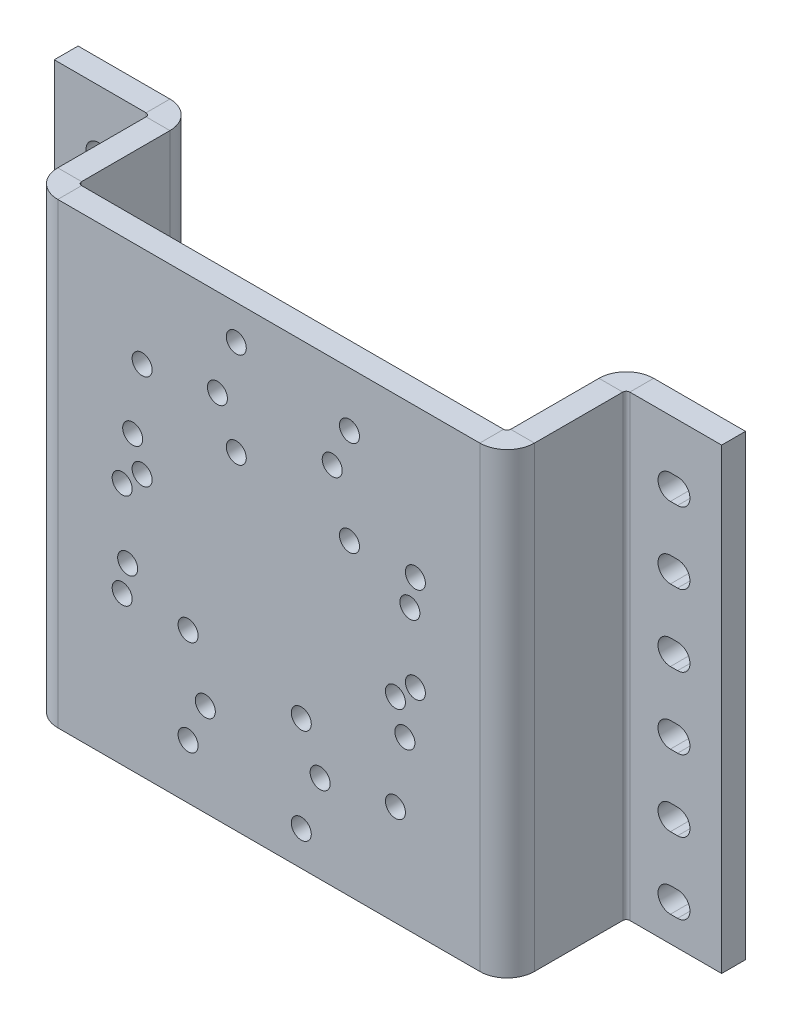
SolidWorks part; units mm, degrees
note: '?' marks a value the reader was unsure of. The reader was unsure of these and kept them because the rebuilt part matched: flange length of "Aresta-Flange1", "Aresta-Flange2", "Aresta-Flange3", "Aresta-Flange4".
material "AISI 1020"
ref_plane "Plano frontal" through (0, 0, 0) normal (0, 0, 1) x (1, 0, 0)
ref_plane "Plano superior" through (0, 0, 0) normal (0, 1, 0) x (1, 0, 0)
ref_plane "Plano direito" through (0, 0, 0) normal (1, 0, 0) x (0, 0, -1)
sketch "Esboço1" plane through (0, 0, 0) normal (0, 0, 1) x (1, 0, 0)
  line L1 (-50, 48) -> (50, 48)
  line L2 (-50, 48) -> (-50, -48)
  line L3 (-50, -48) -> (50, -48)
  line L4 (50, 48) -> (50, -48)
  line L5 (-50, 48) -> (50, -48) construction
  line L6 (-50, -48) -> (50, 48) construction
  point P0 (0, 0)
  dimension "D1" = 100
  dimension "D2" = 96
base flange "Flange-base1" sketch "Esboço1" thickness 5 reverse thickness direction no parameters "D1"=0.7366
edge flange "Aresta-Flange1" sketch "Esboço8" flange angle 90 flange length 30 flange position material inside bend radius 0.7366 thickness 5 relief rectangular parameters "D6"=10
sketch "Esboço8" plane through (50, 0, -5) normal (-1, 0, 0) x (0, 1, 0)
  line L2 (-48, 0) -> (-48, 25)
  line L3 (-48, 25) -> (48, 25)
  line L4 (48, 25) -> (48, 0)
  line L5 (48, 0) -> (-48, 0) construction
  line L6 (48, 0) -> (-48, 0)
bend "DobradeAresta1" bend radius 0.7366 bend angle 90 parameters "D5"=1
edge flange "Aresta-Flange2" sketch "Esboço11" flange angle 90 flange length 25 flange position material inside bend radius 0.7366 thickness 5 relief rectangular parameters "D6"=10
sketch "Esboço11" plane through (50, 0, -30) normal (0, 0, -1) x (0, 1, 0)
  line L2 (-48, 0) -> (-48, 20)
  line L3 (-48, 20) -> (48, 20)
  line L4 (48, 20) -> (48, 0)
  line L7 (48, 0) -> (-48, 0) construction
  line L8 (48, 0) -> (-48, 0)
bend "DobradeAresta2" bend radius 0.7366 bend angle 90 parameters "D5"=2
edge flange "Aresta-Flange3" sketch "Esboço14" flange angle 90 flange length 30 flange position material inside bend radius 0.7366 thickness 5 relief rectangular parameters "D6"=10
sketch "Esboço14" plane through (-50, 0, -5) normal (1, 0, 0) x (0, -1, 0)
  line L2 (-48, 0) -> (-48, 25)
  line L3 (-48, 25) -> (48, 25)
  line L4 (48, 25) -> (48, 0)
  line L5 (48, 0) -> (-48, 0) construction
  line L6 (48, 0) -> (-48, 0)
bend "DobradeAresta3" bend radius 0.7366 bend angle 90 parameters "D5"=3
edge flange "Aresta-Flange4" sketch "Esboço19" flange angle 90 flange length 25 flange position material inside bend radius 0.7366 thickness 5 relief rectangular parameters "D6"=10
sketch "Esboço19" plane through (-50, 0, -30) normal (0, 0, -1) x (0, -1, 0)
  line L0 (48, 0) -> (-48, 0) construction
  line L1 (48, 0) -> (-48, 0)
  line L2 (-48, 0) -> (-48, 20)
  line L3 (-48, 20) -> (48, 20)
  line L4 (48, 20) -> (48, 0)
bend "DobradeAresta4" bend radius 0.7366 bend angle 90 parameters "D5"=4
sketch "Esboço20" plane through (0, 0, 0) normal (0, 0, 1) x (1, 0, 0)
  line L0 (0, 0) -> (-10.7736, 29.6003) construction
  line L1 (0, -31.5) -> (0, 31.5) construction
  line L2 (0, 10) -> (-6.8178, 40.7533) construction
  line L3 (0, -10) -> (-6.8178, 20.7533) construction
  circle A3 centre (0, 0) radius 31.5 construction
  circle A4 centre (-10.7736, 29.6003) radius 2.5 construction
  circle A5 centre (0, 10) radius 31.5 construction
  circle A6 centre (-6.8178, 40.7533) radius 2.5 construction
  circle A7 centre (0, -10) radius 31.5 construction
  circle A8 centre (-6.8178, 20.7533) radius 2.5 construction
  dimension "D1" = 63
  dimension "D2" = 5
  dimension "D3" = 20
  dimension "D4" = 10
  dimension "D5" = 12.5
  dimension "D7" = 12.5
  dimension "D6" = 10
hole_wizard "Furo de diâmetro Ø4.2 (4.2)1" positions "3DSketch1" profile "Esboço21" hole size "Ø4.2" standard "DIN" end condition through all
sketch3d "3DSketch1"
  point P0 (-10.7736, 29.6003, 0)
sketch "Esboço21" plane through (-10.7736, 29.6003, 0) normal (1, 0, 0) x (0, -1, 0)
  line L0 (0, 0) -> (0, 30)
  line L1 (0, 30) -> (2.1, 30)
  line L2 (2.1, 30) -> (2.1, 0)
  line L5 (2.1, 0) -> (0, 0)
  line L11 (0, -6.35) -> (0, 107.95) construction
  dimension "Thru Hole Dia." = 4.2
  dimension "Thru Hole Depth" = 30
ref_axis "Eixo1" through (0, 0, -31.5) along (0, 0, 1)?
pattern_circular "PadrãoCircular1" count 8 over 360 about axis through (0, 0, 0) along (0, 0, 1) of "Furo de diâmetro Ø4.2 (4.2)1"
hole_wizard "Furo de diâmetro Ø4.2 (4.2)2" positions "3DSketch2" profile "Esboço22" hole size "Ø4.2" standard "DIN" end condition through all
sketch3d "3DSketch2"
  point P0 (-6.8178, 40.7533, 0)
sketch "Esboço22" plane through (-6.8178, 40.7533, 0) normal (1, 0, 0) x (0, -1, 0)
  line L0 (0, 0) -> (0, 30)
  line L1 (0, 30) -> (2.1, 30)
  line L2 (2.1, 30) -> (2.1, 0)
  line L5 (2.1, 0) -> (0, 0)
  line L11 (0, -6.35) -> (0, 107.95) construction
  dimension "Thru Hole Dia." = 4.2
  dimension "Thru Hole Depth" = 30
ref_axis "Eixo2" through (0, 10, 0) along (0, 0, 1)?
pattern_circular "PadrãoCircular2" count 8 over 360 about axis through (0, 10, 0) along (0, 0, 1) of "Furo de diâmetro Ø4.2 (4.2)2"
hole_wizard "Furo de diâmetro Ø4.2 (4.2)3" positions "3DSketch3" profile "Esboço23" hole size "Ø4.2" standard "DIN" end condition through all
sketch3d "3DSketch3"
  point P0 (-6.8178, 20.7533, 0)
sketch "Esboço23" plane through (-6.8178, 20.7533, 0) normal (1, 0, 0) x (0, -1, 0)
  line L0 (0, 0) -> (0, 30)
  line L1 (0, 30) -> (2.1, 30)
  line L2 (2.1, 30) -> (2.1, 0)
  line L5 (2.1, 0) -> (0, 0)
  line L11 (0, -6.35) -> (0, 107.95) construction
  dimension "Thru Hole Dia." = 4.2
  dimension "Thru Hole Depth" = 30
ref_axis "Eixo3" through (0, -10, 0) along (0, 0, 1)?
pattern_circular "PadrãoCircular3" count 8 over 360 about axis through (0, -10, 0) along (0, 0, 1) of "Furo de diâmetro Ø4.2 (4.2)3"
sketch "Esboço24" plane through (0, 0, -25) normal (0, 0, 1) x (1, 0, 0)
  line L0 (-60, 48) -> (-60, -48) construction
  line L1 (-60.75, -40) -> (-59.25, -40) construction
  line L3 (-70, 48) -> (-50.7366, 48) construction
  line L4 (-50.7366, -48) -> (-70, -48) construction
  line L5 (-70, -48) -> (-70, 48) construction
  line L7 (-60.75, -37.4) -> (-59.25, -37.4)
  line L8 (-60.75, -42.6) -> (-59.25, -42.6)
  circle A5 centre (-60, -40) radius 2.6 construction
  arc A6 (-60.75, -37.4) -> (-60.75, -42.6) centre (-60.75, -40) ccw
  arc A7 (-59.25, -42.6) -> (-59.25, -37.4) centre (-59.25, -40) ccw
  point P11 (-60, -40)
  dimension "D3" = 40
  dimension "D2" = 5.2
  dimension "D1" = 10
  dimension "D4" = 1.5
extrude "Corte-extrusão1" cut sketch "Esboço24" against normal up to next normal cut yes
pattern_linear "Padrão linear2" count 6 spacing 15 along (0, 1, 0) of "Corte-extrusão1"
mirror "Espelhar2" about plane through (0, 0, 0) normal (1, 0, 0) of "Padrão linear2", "Corte-extrusão1"
sketch "Curva-Linhas1" [suppressed] plane through (0, 0, 0) normal (0, 1, 0) x (1, 0, 0)
sketch "Caixa delimitadora1" [suppressed] plane through (0, 0, 0) normal (0, 1, 0) x (1, 0, 0)
sheet metal parameters "Chapa metálica1" thickness 5 parameters "D1"=0.7366
flat pattern "Padrão-Plano1" [suppressed]
sketch "Curva-Linhas2" plane through (0, 0, 0) normal (0, 1, 0) x (1, 0, 0)
sketch3d "Caixa delimitadora2" [suppressed]
  line L0 (-50, 75, 0) -> (-50, -75, 0) construction
  line L1 (50, 75, 0) -> (50, -75, 0) construction
  line L2 (-50, 75, 0) -> (50, 75, 0) construction
  line L3 (-50, -75, 0) -> (50, -75, 0) construction
sheet metal parameters "Chapa metálica2" thickness 5 parameters "D1"=0.7366
flat pattern "Padrão-Plano1"
sketch "Curva-Linhas2" plane through (0, 0, 0) normal (0, 0, 1) x (1, 0, 0)
  line L0 (46.8054, -75) -> (46.8054, 75) construction
  line L1 (46.8054, -75) -> (46.8054, 75) construction
sketch3d "Caixa delimitadora2" [suppressed]
  line L0 (73.6108, 75, 0) -> (73.6108, -75, 0) construction
  line L1 (-50, 75, 0) -> (-50, -75, 0) construction
  line L2 (73.6108, 75, 0) -> (-50, 75, 0) construction
  line L3 (73.6108, -75, 0) -> (-50, -75, 0) construction
bend of the flat pattern "Planificar-<DobradeAresta1>1"
sheet metal parameters "Chapa metálica3" thickness 5 parameters "D1"=0.7366
flat pattern "Padrão-Plano1"
sketch "Curva-Linhas2" plane through (0, 0, 0) normal (0, 0, 1) x (1, 0, 0)
  line L0 (46.8054, -75) -> (46.8054, 75) construction
  line L1 (46.8054, -75) -> (46.8054, 75) construction
  line L2 (70.4163, -75) -> (70.4163, 75) construction
  line L3 (70.4163, -75) -> (70.4163, 75) construction
sketch3d "Caixa delimitadora2" [suppressed]
  line L0 (92.2217, 75, 0) -> (92.2217, -75, 0) construction
  line L1 (-50, 75, 0) -> (-50, -75, 0) construction
  line L2 (92.2217, 75, 0) -> (-50, 75, 0) construction
  line L3 (92.2217, -75, 0) -> (-50, -75, 0) construction
bend of the flat pattern "Planificar-<DobradeAresta1>1"
bend of the flat pattern "Planificar-<DobradeAresta2>1"
sheet metal parameters "Chapa metálica4" thickness 5 parameters "D1"=0.7366
flat pattern "Padrão-Plano1"
sketch "Curva-Linhas2" plane through (0, 0, 0) normal (0, 0, 1) x (1, 0, 0)
  line L0 (46.8054, -75) -> (46.8054, 75) construction
  line L1 (46.8054, -75) -> (46.8054, 75) construction
  line L2 (70.4163, -75) -> (70.4163, 75) construction
  line L3 (70.4163, -75) -> (70.4163, 75) construction
  line L4 (-46.8054, 75) -> (-46.8054, -75) construction
  line L5 (-46.8054, 75) -> (-46.8054, -75) construction
sketch3d "Caixa delimitadora2" [suppressed]
  line L0 (-73.6108, -75, 0) -> (92.2217, -75, 0) construction
  line L1 (-73.6108, 75, 0) -> (92.2217, 75, 0) construction
  line L2 (-73.6108, -75, 0) -> (-73.6108, 75, 0) construction
  line L3 (92.2217, -75, 0) -> (92.2217, 75, 0) construction
bend of the flat pattern "Planificar-<DobradeAresta1>1"
bend of the flat pattern "Planificar-<DobradeAresta2>1"
bend of the flat pattern "Planificar-<DobradeAresta3>1"
sheet metal parameters "Chapa metálica5" thickness 5 parameters "D1"=0.7366
flat pattern "Padrão-Plano1"
sketch "Curva-Linhas2" plane through (0, 0, 0) normal (0, 0, 1) x (1, 0, 0)
  line L0 (46.8054, -50) -> (46.8054, 50) construction
  line L1 (46.8054, -50) -> (46.8054, 50) construction
  line L2 (70.4163, -50) -> (70.4163, 50) construction
  line L3 (70.4163, -50) -> (70.4163, 50) construction
  line L4 (-46.8054, 50) -> (-46.8054, -50) construction
  line L5 (-46.8054, 50) -> (-46.8054, -50) construction
  line L6 (-70.4163, 50) -> (-70.4163, -50) construction
  line L7 (-70.4163, 50) -> (-70.4163, -50) construction
sketch3d "Caixa delimitadora2" [suppressed]
  line L0 (-92.2217, -50, 0) -> (92.2217, -50, 0) construction
  line L1 (-92.2217, 50, 0) -> (92.2217, 50, 0) construction
  line L2 (-92.2217, -50, 0) -> (-92.2217, 50, 0) construction
  line L3 (92.2217, -50, 0) -> (92.2217, 50, 0) construction
bend of the flat pattern "Planificar-<DobradeAresta1>1"
bend of the flat pattern "Planificar-<DobradeAresta2>1"
bend of the flat pattern "Planificar-<DobradeAresta3>1"
bend of the flat pattern "Planificar-<DobradeAresta4>1"
sheet metal parameters "Chapa metálica6" thickness 5 parameters "D1"=0.7366
flat pattern "Padrão-Plano1"
sketch "Curva-Linhas2" plane through (0, 0, 0) normal (0, 0, 1) x (1, 0, 0)
  line L0 (46.8054, -50) -> (46.8054, 50) construction
  line L1 (46.8054, -50) -> (46.8054, 50) construction
  line L2 (70.4163, -50) -> (70.4163, 50) construction
  line L3 (70.4163, -50) -> (70.4163, 50) construction
  line L4 (-46.8054, 50) -> (-46.8054, -50) construction
  line L5 (-46.8054, 50) -> (-46.8054, -50) construction
  line L6 (-70.4163, 50) -> (-70.4163, -50) construction
  line L7 (-70.4163, 50) -> (-70.4163, -50) construction
sketch3d "Caixa delimitadora2" [suppressed]
  line L0 (-92.2217, -50, 0) -> (92.2217, -50, 0) construction
  line L1 (-92.2217, 50, 0) -> (92.2217, 50, 0) construction
  line L2 (-92.2217, -50, 0) -> (-92.2217, 50, 0) construction
  line L3 (92.2217, -50, 0) -> (92.2217, 50, 0) construction
bend of the flat pattern "Planificar-<DobradeAresta1>1"
bend of the flat pattern "Planificar-<DobradeAresta2>1"
bend of the flat pattern "Planificar-<DobradeAresta3>1"
bend of the flat pattern "Planificar-<DobradeAresta4>1"
sheet metal parameters "Chapa metálica7" thickness 5 parameters "D1"=0.7366
flat pattern "Padrão-Plano1"
sketch "Curva-Linhas2" plane through (0, 0, 0) normal (0, 0, 1) x (1, 0, 0)
  line L0 (46.8054, -50) -> (46.8054, 50) construction
  line L1 (46.8054, -50) -> (46.8054, 50) construction
  line L2 (70.4163, -50) -> (70.4163, 50) construction
  line L3 (70.4163, -50) -> (70.4163, 50) construction
  line L4 (-46.8054, 50) -> (-46.8054, -50) construction
  line L5 (-46.8054, 50) -> (-46.8054, -50) construction
  line L6 (-70.4163, 50) -> (-70.4163, -50) construction
  line L7 (-70.4163, 50) -> (-70.4163, -50) construction
sketch3d "Caixa delimitadora2" [suppressed]
  line L0 (-92.2217, -50, 0) -> (92.2217, -50, 0) construction
  line L1 (-92.2217, 50, 0) -> (92.2217, 50, 0) construction
  line L2 (-92.2217, -50, 0) -> (-92.2217, 50, 0) construction
  line L3 (92.2217, -50, 0) -> (92.2217, 50, 0) construction
bend of the flat pattern "Planificar-<DobradeAresta1>1"
bend of the flat pattern "Planificar-<DobradeAresta2>1"
bend of the flat pattern "Planificar-<DobradeAresta3>1"
bend of the flat pattern "Planificar-<DobradeAresta4>1"
sheet metal parameters "Chapa metálica8" thickness 5 parameters "D1"=0.7366
flat pattern "Padrão-Plano1"
sketch "Curva-Linhas2" plane through (0, 0, 0) normal (0, 0, 1) x (1, 0, 0)
  line L0 (46.8054, -50) -> (46.8054, 50) construction
  line L1 (46.8054, -50) -> (46.8054, 50) construction
  line L2 (70.4163, -50) -> (70.4163, 50) construction
  line L3 (70.4163, -50) -> (70.4163, 50) construction
  line L4 (-46.8054, 50) -> (-46.8054, -50) construction
  line L5 (-46.8054, 50) -> (-46.8054, -50) construction
  line L6 (-70.4163, 50) -> (-70.4163, -50) construction
  line L7 (-70.4163, 50) -> (-70.4163, -50) construction
sketch3d "Caixa delimitadora2" [suppressed]
  line L0 (-92.2217, -50, 0) -> (92.2217, -50, 0) construction
  line L1 (-92.2217, 50, 0) -> (92.2217, 50, 0) construction
  line L2 (-92.2217, -50, 0) -> (-92.2217, 50, 0) construction
  line L3 (92.2217, -50, 0) -> (92.2217, 50, 0) construction
bend of the flat pattern "Planificar-<DobradeAresta1>1"
bend of the flat pattern "Planificar-<DobradeAresta2>1"
bend of the flat pattern "Planificar-<DobradeAresta3>1"
bend of the flat pattern "Planificar-<DobradeAresta4>1"
sheet metal parameters "Chapa metálica9" thickness 5 parameters "D1"=0.7366
flat pattern "Padrão-Plano1"
sketch "Curva-Linhas2" plane through (0, 0, 0) normal (0, 0, 1) x (1, 0, 0)
  line L0 (46.8054, -50) -> (46.8054, 50) construction
  line L1 (46.8054, -50) -> (46.8054, 50) construction
  line L2 (70.4163, -50) -> (70.4163, 50) construction
  line L3 (70.4163, -50) -> (70.4163, 50) construction
  line L4 (-46.8054, 50) -> (-46.8054, -50) construction
  line L5 (-46.8054, 50) -> (-46.8054, -50) construction
  line L6 (-70.4163, 50) -> (-70.4163, -50) construction
  line L7 (-70.4163, 50) -> (-70.4163, -50) construction
sketch3d "Caixa delimitadora2" [suppressed]
  line L0 (-92.2217, -50, 0) -> (92.2217, -50, 0) construction
  line L1 (-92.2217, 50, 0) -> (92.2217, 50, 0) construction
  line L2 (-92.2217, -50, 0) -> (-92.2217, 50, 0) construction
  line L3 (92.2217, -50, 0) -> (92.2217, 50, 0) construction
bend of the flat pattern "Planificar-<DobradeAresta1>1"
bend of the flat pattern "Planificar-<DobradeAresta2>1"
bend of the flat pattern "Planificar-<DobradeAresta3>1"
bend of the flat pattern "Planificar-<DobradeAresta4>1"
sheet metal parameters "Chapa metálica10" thickness 5 parameters "D1"=0.7366
flat pattern "Padrão-Plano1"
sketch "Curva-Linhas2" plane through (0, 0, 0) normal (0, 0, 1) x (1, 0, 0)
  line L0 (46.8054, -50) -> (46.8054, 50) construction
  line L1 (46.8054, -50) -> (46.8054, 50) construction
  line L2 (70.4163, -50) -> (70.4163, 50) construction
  line L3 (70.4163, -50) -> (70.4163, 50) construction
  line L4 (-46.8054, 50) -> (-46.8054, -50) construction
  line L5 (-46.8054, 50) -> (-46.8054, -50) construction
  line L6 (-70.4163, 50) -> (-70.4163, -50) construction
  line L7 (-70.4163, 50) -> (-70.4163, -50) construction
sketch3d "Caixa delimitadora2" [suppressed]
  line L0 (-92.2217, -50, 0) -> (92.2217, -50, 0) construction
  line L1 (-92.2217, 50, 0) -> (92.2217, 50, 0) construction
  line L2 (-92.2217, -50, 0) -> (-92.2217, 50, 0) construction
  line L3 (92.2217, -50, 0) -> (92.2217, 50, 0) construction
bend of the flat pattern "Planificar-<DobradeAresta1>1"
bend of the flat pattern "Planificar-<DobradeAresta2>1"
bend of the flat pattern "Planificar-<DobradeAresta3>1"
bend of the flat pattern "Planificar-<DobradeAresta4>1"
sheet metal parameters "Chapa metálica11" thickness 5 parameters "D1"=0.7366
flat pattern "Padrão-Plano1" [suppressed]
sketch "Curva-Linhas2" plane through (0, 0, 0) normal (0, 0, 1) x (1, 0, 0)
  line L0 (46.8054, -50) -> (46.8054, 50) construction
  line L1 (46.8054, -50) -> (46.8054, 50) construction
  line L2 (70.4163, -50) -> (70.4163, 50) construction
  line L3 (70.4163, -50) -> (70.4163, 50) construction
  line L4 (-46.8054, 50) -> (-46.8054, -50) construction
  line L5 (-46.8054, 50) -> (-46.8054, -50) construction
  line L6 (-70.4163, 50) -> (-70.4163, -50) construction
  line L7 (-70.4163, 50) -> (-70.4163, -50) construction
sketch3d "Caixa delimitadora2" [suppressed]
  line L0 (-92.2217, -50, 0) -> (92.2217, -50, 0) construction
  line L1 (-92.2217, 50, 0) -> (92.2217, 50, 0) construction
  line L2 (-92.2217, -50, 0) -> (-92.2217, 50, 0) construction
  line L3 (92.2217, -50, 0) -> (92.2217, 50, 0) construction
bend of the flat pattern "Planificar-<DobradeAresta1>1"
bend of the flat pattern "Planificar-<DobradeAresta2>1"
bend of the flat pattern "Planificar-<DobradeAresta3>1"
bend of the flat pattern "Planificar-<DobradeAresta4>1"
sketch "Esboço24-2" [suppressed] plane through (-22.2217, 0, 0) normal (0, 0, 1) x (1, 0, 0)
  line L0 (-60, 50) -> (-60, -50) construction
  line L5 (-70, -50) -> (-70, 50) construction
  circle A0 centre (-60, 0) radius 2.5 construction
  dimension "D3" = 5
  dimension "D1" = 10
sheet metal parameters "Chapa metálica15" thickness 5 parameters "D1"=0.7366
flat pattern "Padrão-Plano1" [suppressed]
sketch "Curva-Linhas2" plane through (0, 0, 0) normal (0, 0, 1) x (1, 0, 0)
  line L0 (46.8054, -50) -> (46.8054, 50) construction
  line L1 (46.8054, -50) -> (46.8054, 50) construction
  line L2 (70.4163, -50) -> (70.4163, 50) construction
  line L3 (70.4163, -50) -> (70.4163, 50) construction
  line L4 (-46.8054, 50) -> (-46.8054, -50) construction
  line L5 (-46.8054, 50) -> (-46.8054, -50) construction
  line L6 (-70.4163, 50) -> (-70.4163, -50) construction
  line L7 (-70.4163, 50) -> (-70.4163, -50) construction
sketch3d "Caixa delimitadora2" [suppressed]
  line L0 (-92.2217, -50, 0) -> (92.2217, -50, 0) construction
  line L1 (-92.2217, 50, 0) -> (92.2217, 50, 0) construction
  line L2 (-92.2217, -50, 0) -> (-92.2217, 50, 0) construction
  line L3 (92.2217, -50, 0) -> (92.2217, 50, 0) construction
bend of the flat pattern "Planificar-<DobradeAresta1>1"
bend of the flat pattern "Planificar-<DobradeAresta2>1"
bend of the flat pattern "Planificar-<DobradeAresta3>1"
bend of the flat pattern "Planificar-<DobradeAresta4>1"
sketch "Esboço24-2" [suppressed] plane through (-22.2217, 0, 0) normal (0, 0, 1) x (1, 0, 0)
  line L0 (-60, 50) -> (-60, -50) construction
  line L1 (-60.75, 0) -> (-59.25, 0) construction
  line L2 (-60.75, 2.65) -> (-59.25, 2.65)
  line L5 (-70, -50) -> (-70, 50) construction
  line L6 (-60.75, -2.65) -> (-59.25, -2.65)
  circle A0 centre (-60, 0) radius 2.65 construction
  arc A3 (-60.75, 2.65) -> (-60.75, -2.65) centre (-60.75, 0) ccw
  arc A4 (-59.25, -2.65) -> (-59.25, 2.65) centre (-59.25, 0) ccw
  point P10 (-60, 0)
  dimension "D3" = 5.3
  dimension "D1" = 10
  dimension "D2" = 1.5
sheet metal parameters "Chapa metálica16" thickness 5 parameters "D1"=0.7366
flat pattern "Padrão-Plano1" [suppressed]
sketch "Curva-Linhas2" plane through (0, 0, 0) normal (0, 0, 1) x (1, 0, 0)
  line L0 (46.8054, -48) -> (46.8054, 48) construction
  line L1 (46.8054, -48) -> (46.8054, 48) construction
  line L2 (70.4163, -48) -> (70.4163, 48) construction
  line L3 (70.4163, -48) -> (70.4163, 48) construction
  line L4 (-46.8054, 48) -> (-46.8054, -48) construction
  line L5 (-46.8054, 48) -> (-46.8054, -48) construction
  line L6 (-70.4163, 48) -> (-70.4163, -48) construction
  line L7 (-70.4163, 48) -> (-70.4163, -48) construction
sketch3d "Caixa delimitadora2" [suppressed]
  line L0 (-92.2217, -48, 0) -> (92.2217, -48, 0) construction
  line L1 (-92.2217, 48, 0) -> (92.2217, 48, 0) construction
  line L2 (-92.2217, -48, 0) -> (-92.2217, 48, 0) construction
  line L3 (92.2217, -48, 0) -> (92.2217, 48, 0) construction
bend of the flat pattern "Planificar-<DobradeAresta1>1"
bend of the flat pattern "Planificar-<DobradeAresta2>1"
bend of the flat pattern "Planificar-<DobradeAresta3>1"
bend of the flat pattern "Planificar-<DobradeAresta4>1"
sketch "Esboço24-2" plane through (-22.2217, 0, 0) normal (0, 0, 1) x (1, 0, 0)
  line L0 (-60, 48) -> (-60, -48) construction
  line L1 (-60.75, -40) -> (-59.25, -40) construction
  line L5 (-70, -48) -> (-70, 48) construction
  line L7 (-60.75, -37.4) -> (-59.25, -37.4)
  line L8 (-60.75, -42.6) -> (-59.25, -42.6)
  circle A5 centre (-60, -40) radius 2.6 construction
  arc A6 (-60.75, -37.4) -> (-60.75, -42.6) centre (-60.75, -40) ccw
  arc A7 (-59.25, -42.6) -> (-59.25, -37.4) centre (-59.25, -40) ccw
  point P11 (-60, -40)
  dimension "D3" = 40
  dimension "D2" = 5.2
  dimension "D1" = 10
  dimension "D4" = 1.5
sheet metal parameters "Chapa metálica17" thickness 5 parameters "D1"=0.7366
flat pattern "Padrão-Plano1" [suppressed]
sketch "Curva-Linhas2" plane through (0, 0, 0) normal (0, 0, 1) x (1, 0, 0)
  line L0 (46.8054, -48) -> (46.8054, 48) construction
  line L1 (46.8054, -48) -> (46.8054, 48) construction
  line L2 (70.4163, -48) -> (70.4163, 48) construction
  line L3 (70.4163, -48) -> (70.4163, 48) construction
  line L4 (-46.8054, 48) -> (-46.8054, -48) construction
  line L5 (-46.8054, 48) -> (-46.8054, -48) construction
  line L6 (-70.4163, 48) -> (-70.4163, -48) construction
  line L7 (-70.4163, 48) -> (-70.4163, -48) construction
sketch3d "Caixa delimitadora2" [suppressed]
  line L0 (-92.2217, -48, 0) -> (92.2217, -48, 0) construction
  line L1 (-92.2217, 48, 0) -> (92.2217, 48, 0) construction
  line L2 (-92.2217, -48, 0) -> (-92.2217, 48, 0) construction
  line L3 (92.2217, -48, 0) -> (92.2217, 48, 0) construction
bend of the flat pattern "Planificar-<DobradeAresta1>1"
bend of the flat pattern "Planificar-<DobradeAresta2>1"
bend of the flat pattern "Planificar-<DobradeAresta3>1"
bend of the flat pattern "Planificar-<DobradeAresta4>1"
sketch "Esboço24-2" plane through (-22.2217, 0, 0) normal (0, 0, 1) x (1, 0, 0)
  line L0 (-60, 48) -> (-60, -48) construction
  line L1 (-60.75, -40) -> (-59.25, -40) construction
  line L5 (-70, -48) -> (-70, 48) construction
  line L7 (-60.75, -37.4) -> (-59.25, -37.4)
  line L8 (-60.75, -42.6) -> (-59.25, -42.6)
  circle A5 centre (-60, -40) radius 2.6 construction
  arc A6 (-60.75, -37.4) -> (-60.75, -42.6) centre (-60.75, -40) ccw
  arc A7 (-59.25, -42.6) -> (-59.25, -37.4) centre (-59.25, -40) ccw
  point P11 (-60, -40)
  dimension "D3" = 40
  dimension "D2" = 5.2
  dimension "D1" = 10
  dimension "D4" = 1.5
